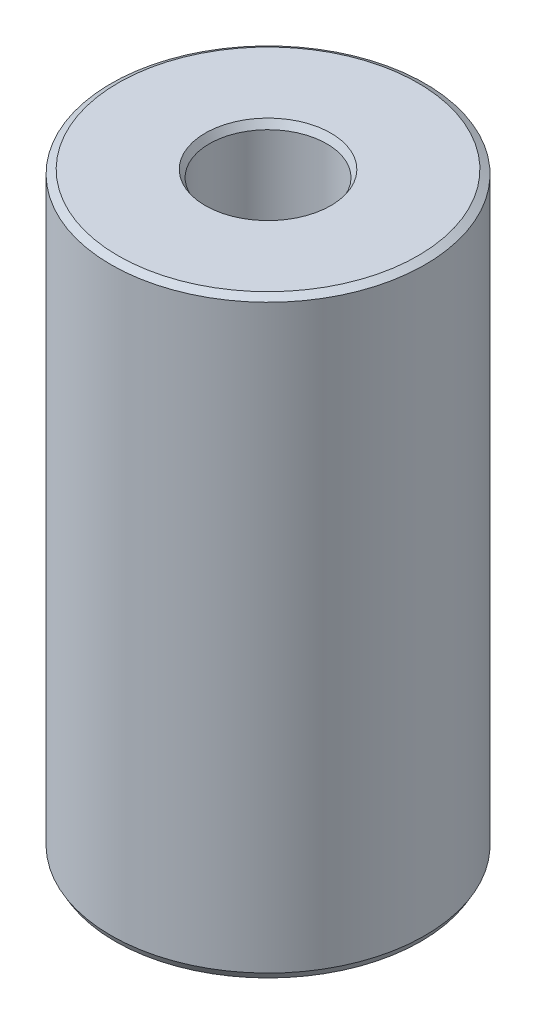
SolidWorks part; units mm, degrees
ref_plane "Front Plane" through (0, 0, 0) normal (0, 0, 1) x (1, 0, 0)
ref_plane "Top Plane" through (0, 0, 0) normal (0, 1, 0) x (1, 0, 0)
ref_plane "Right Plane" through (0, 0, 0) normal (1, 0, 0) x (0, 0, -1)
sketch "Sketch1" plane through (0, 0, 0) normal (0, 1, 0) x (1, 0, 0)
  circle A0 centre (0, 0) radius 25
  dimension "SLEEVE_OD" = 50
extrude "Boss-Extrude1" add sketch "Sketch1" along normal blind 94.3124
sketch "Sketch2" plane through (0, 0, 0) normal (0, 1, 0) x (1, 0, 0)
  circle A0 centre (0, 0) radius 9.348
  dimension "BORE_D" = 18.696
extrude "Cut-Extrude1" cut sketch "Sketch2" along normal through all
chamfer "Chamfer1" distance 0.6571 angle 60 4 edges at (0, 94.3124, 9.348) (0, 0, 9.348) (0, 0, 25) (0, 94.3124, 25) first distance on face at (0, 94.3124, 9.348) first distance on face at (0, 0, 9.348) first distance on face at (0, 94.3124, 25)
